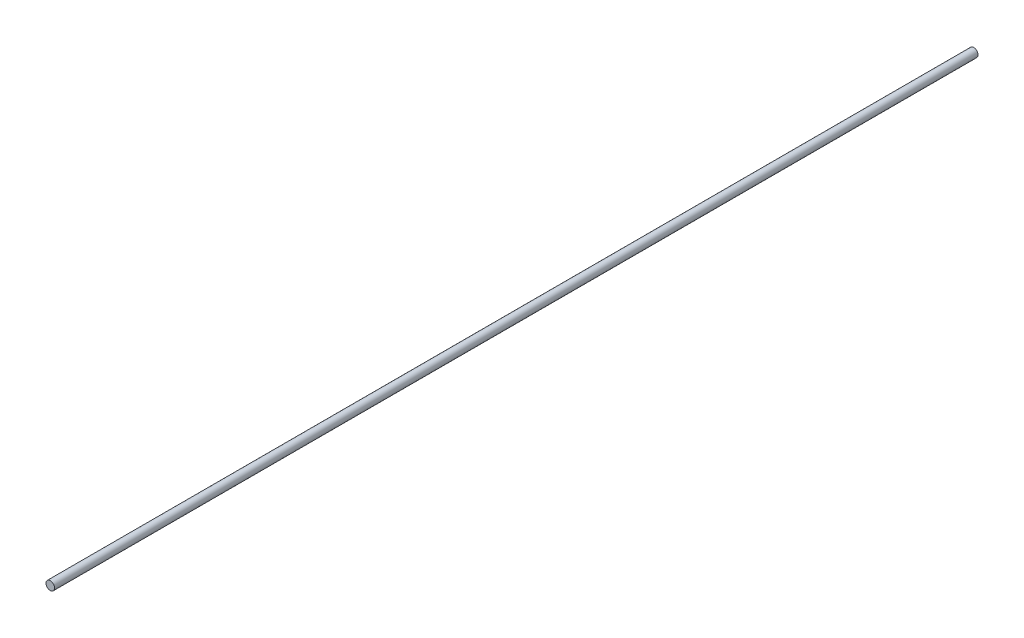
SolidWorks part; units mm, degrees
material "AISI 1020"
ref_plane "Front Plane" through (0, 0, 0) normal (0, 0, 1) x (1, 0, 0)
ref_plane "Top Plane" through (0, 0, 0) normal (0, 1, 0) x (1, 0, 0)
ref_plane "Right Plane" through (0, 0, 0) normal (1, 0, 0) x (0, 0, -1)
sketch "Sketch1" plane through (0, 0, 0) normal (0, 0, 1) x (1, 0, 0)
  circle A0 centre (0, 0) radius 7.9375
  dimension "D1" = 15.875
extrude "Boss-Extrude1" add sketch "Sketch1" along normal blind 2254.25
sketch "Sketch2" plane through (0, 0, 0) normal (0, 0, -1) x (-1, 0, 0)
  circle A0 centre (0, 0) radius 7.9375
extrude "Cut-Extrude1" cut sketch "Sketch2" against normal blind 539.75
